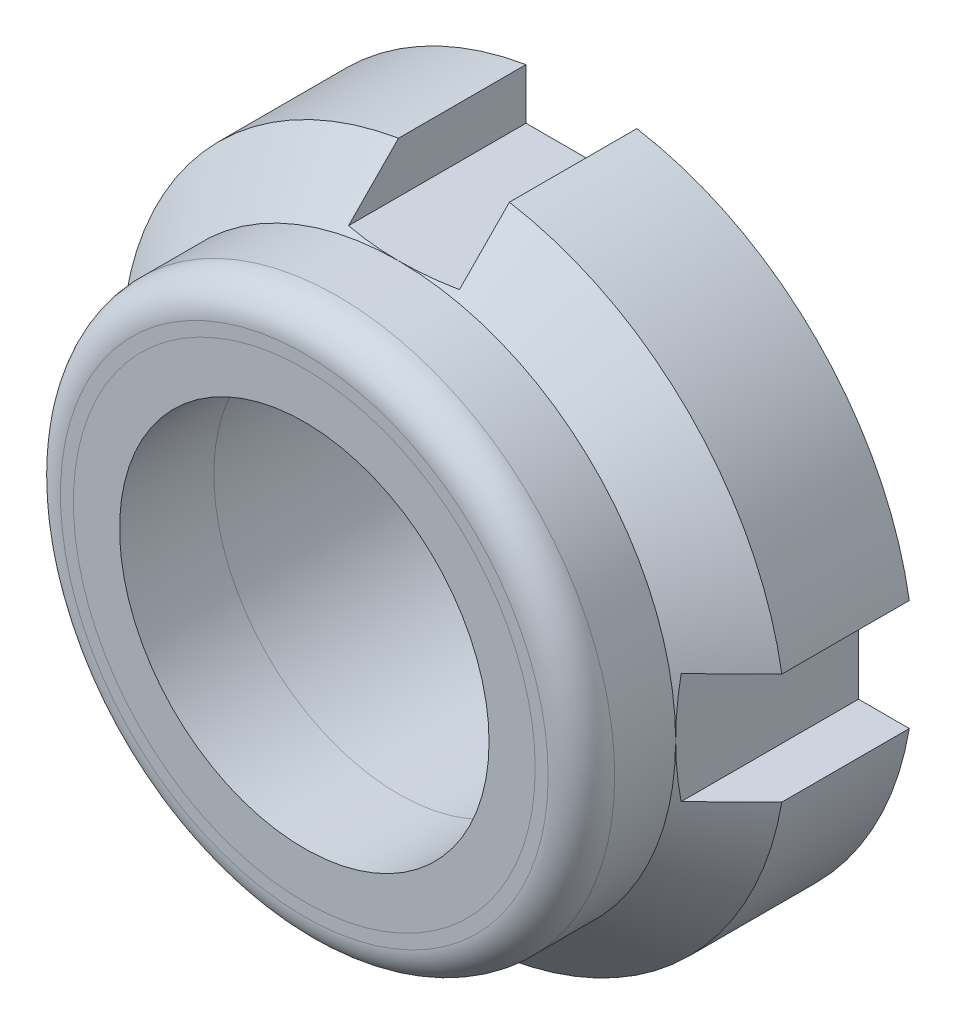
SolidWorks part; units mm, degrees
ref_plane "Front Plane" through (0, 0, 0) normal (0, 0, 1) x (1, 0, 0)
ref_plane "Top Plane" through (0, 0, 0) normal (0, 1, 0) x (1, 0, 0)
ref_plane "Right Plane" through (0, 0, 0) normal (1, 0, 0) x (0, 0, -1)
sketch "Sketch1" plane through (0, 0, 0) normal (0, 0, 1) x (1, 0, 0)
  line L0 (-1.5, -9) -> (1.5, -9) construction
  line L1 (0, 0) -> (0, -9) construction
  line L2 (0, 7.5) -> (0, 5) construction
  circle A0 centre (0, 0) radius 9 construction
  circle A1 centre (0, 0) radius 5 construction
  circle A2 centre (0, 0) radius 7.5 construction
  point P9 (0, -7.5)
  point P11 (0, 6.25)
sketch "Sketch2" plane through (0, 0, 0) normal (1, 0, 0) x (0, 0, -1)
  line L0 (-3.75, 0) -> (3.75, 0) construction
  point P2 (0, 0)
  point P3 (-3.25, 0)
  point P5 (-1.2, 0)
  dimension "M" = 4.95
sketch "Sketch4" plane through (0, 0, 0) normal (0, 0, 1) x (1, 0, 0)
  circle A0 centre (0, 0) radius 9 construction
  circle A1 centre (0, 0) radius 9
  circle A2 centre (0, 0) radius 5 construction
  circle A3 centre (0, 0) radius 5
extrude "Boss-Extrude1" add sketch "Sketch4" along normal up to vertex (3.75 mm away) and the other way up to vertex (3.75 mm away) up to point (0, 0, 3.75) other way up to point (0, 0, -3.75)
sketch "Sketch5" plane through (0, 0, 3.75) normal (0, 0, 1) x (1, 0, 0)
  circle A0 centre (0, 0) radius 7.5 construction
  circle A1 centre (0, 0) radius 9
  circle A2 centre (0, 0) radius 9
  circle A3 centre (0, 0) radius 7.5
  dimension "D1" = 0
extrude "Cut-Extrude1" cut sketch "Sketch5" against normal up to vertex (0.5 mm away) up to point (0, 0, 3.25)
sketch "Sketch16" plane through (0, 0, 0) normal (0, 0, 1) x (1, 0, 0)
  line L1 (-1.5, -7.5) -> (1.5, -7.5)
  line L2 (-1.5, -7.5) -> (-1.5, -9)
  line L3 (-1.5, -9) -> (1.5, -9)
  line L4 (1.5, -7.5) -> (1.5, -9)
extrude "Cut-Extrude7" cut sketch "Sketch16" against normal through all both and the other way through all
pattern_circular "CirPattern1" count 4 over 360 about axis through (0, 0, 3.75) along (0, 0, -1) of "Cut-Extrude7"
sketch "Sketch18" plane through (0, 0, 0) normal (1, 0, 0) x (0, 0, -1)
  line L0 (-1.2, 7.5) -> (0.3, 9)
  line L2 (0.3, 9) -> (-3.75, 9)
  line L4 (-3.75, 0) -> (3.75, 0) construction
  line L5 (0.3, 9) -> (0, 9) construction
  line L6 (-3.75, 7.5) -> (-1.2, 7.5)
  line L14 (-1.2, 7.5) -> (0, 7.5) construction
  line L22 (-3.75, 7.5) -> (-3.75, -7.5) construction
  line L23 (-3.75, 7.5) -> (-3.75, 9)
  dimension "D1" = 45
revolve "Cut-Revolve1" cut sketch "Sketch18" angle 360 about L4
fillet "Fillet1" radius 0.9 1 edges at (7.5, 0, 3.75)
sketch "Sketch19" plane through (0, 0, 3.75) normal (0, 0, 1) x (1, 0, 0)
  circle A1 centre (0, 0) radius 6.25
extrude "Cut-Extrude8" cut sketch "Sketch19" against normal up to vertex (2.55 mm away) up to point (0, 7.5, 1.2)
sketch "Sketch20" plane through (0, 0, 1.2) normal (0, 0, 1) x (1, 0, 0)
  circle A0 centre (0, 0) radius 5 construction
  circle A1 centre (0, 0) radius 6.25
  circle A2 centre (0, 0) radius 6.25
  circle A3 centre (0, 0) radius 5
  dimension "D1" = 0
extrude "Boss-Extrude2" add sketch "Sketch20" along normal up to vertex (2.55 mm away) separate body up to point (0, 0, 3.75)
ref_axis "Center Axis 1" through (0, 0, -0.3) along (0, 0, -1)
ref_plane "Contact Plane 1" through (0, 0, 3.75) normal (0, 0, -1) x (-1, 0, 0)
ref_plane "Contact Plane 2" through (0, 0, -3.75) normal (0, 0, -1) x (-1, 0, 0)
sketch "Sketch8" [suppressed] plane through (0, 0, 3.75) normal (0, 0, 1) x (1, 0, 0)
  circle A0 centre (0, 0) radius 5 construction
  circle A1 centre (0, 0) radius 5
curve "Helix/Spiral1" [suppressed] pitch 1 height 8.5 turns 8.5 parameters "Pitch"=1
sketch "Sketch14" [suppressed] plane through (0, 0, 3.75) normal (0, 0, 1) x (1, 0, 0)
  circle A0 centre (0, 0) radius 5 construction
  circle A4 centre (0, 0) radius 5
sketch "Sketch15" [suppressed] plane through (0, 0, -3.75) normal (0, 0, -1) x (-1, 0, 0)
  circle A3 centre (0, 0) radius 5 construction
  circle A4 centre (0, 0) radius 5
sketch "Sketch9" [suppressed] plane through (0, 0, 0) normal (1, 0, 0) x (0, 0, -1)
  line L0 (-4.6827, 5.1) -> (-4.625, 5)
  line L1 (-4.625, 5) -> (-4.25, 4.3505)
  line L2 (-4.25, 4.3505) -> (-4.125, 4.3505)
  line L3 (-4.125, 4.3505) -> (-3.75, 5)
  line L4 (-3.75, 5) -> (-3.6923, 5.1)
  line L5 (-3.6923, 5.1) -> (-4.6827, 5.1)
  line L6 (-4.1875, 5.1) -> (-4.1875, 4.3505) construction
  line L7 (-4.625, 5) -> (-3.75, 5) construction
  line L8 (-4.4375, 4.6752) -> (-3.9375, 4.6752) construction
  dimension "D1" = 60
  dimension "D2" = 0.1
  dimension "D3" = 0.125
  dimension "D4" = 0.5
sweep "Sweep1" [suppressed] add profiles "Sketch9" path "Helix/Spiral1"
split "Split5" [suppressed] bodies to split 108
split "Split1" [suppressed] bodies to split 127 125
split "Split2" [suppressed] bodies to split 128 125
combine bodies "Combine1" [suppressed] operation type add bodies to combine 110 126
combine bodies "Combine2" [suppressed] operation type add bodies to combine 113 125
extrude "Cut-Extrude5" [suppressed] cut sketch "Sketch14" against normal up to next draft 60
extrude "Cut-Extrude6" [suppressed] cut sketch "Sketch15" against normal up to next draft 60
equation "\"D3@Helix/Spiral1\"=\"Overall Width@Sketch2\"+\"Pitch@Helix/Spiral1\""
equation "\"D3@Sketch9\"=\"Pitch@Helix/Spiral1\"/8"
equation "\"D4@Sketch9\"=\"Pitch@Helix/Spiral1\"/2"
equation "\"M@Sketch2\"=\"Overall Width@Sketch2\"*.66"
equation "\"D1@Fillet1\"=\"OD@Sketch1\"*.05"
